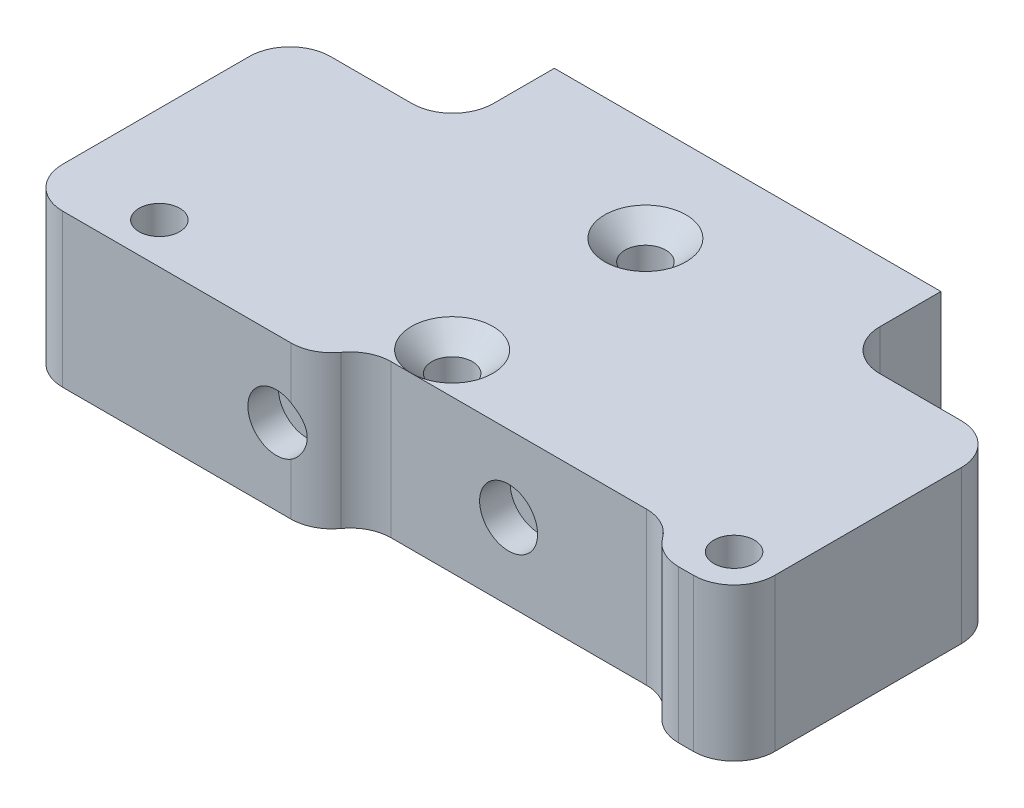
SolidWorks part; units mm, degrees
ref_plane "Front Plane" through (0, 0, 0) normal (0, 0, 1) x (1, 0, 0)
ref_plane "Top Plane" through (0, 0, 0) normal (0, 1, 0) x (1, 0, 0)
ref_plane "Right Plane" through (0, 0, 0) normal (1, 0, 0) x (0, 0, -1)
sketch "Sketch1" plane through (0, 0, 0) normal (0, 1, 0) x (1, 0, 0)
  line L1 (0, 0) -> (-70, 0)
  line L2 (0, 0) -> (0, 34)
  line L3 (0, 34) -> (-70, 34)
  line L4 (-70, 0) -> (-70, 34)
  circle A0 centre (-35.05, 24) radius 2
  circle A1 centre (-35.05, 5) radius 2
  dimension "D5" = 4
  dimension "D6" = 4
  dimension "D7" = 34.95
  dimension "D8" = 34.95
  dimension "D1" = 34
  dimension "D2" = 70
  dimension "D3" = 10
  dimension "D4" = 5
extrude "Boss-Extrude1" add sketch "Sketch1" along normal blind 15
sketch "Sketch4" plane through (0, 0, -34) normal (0, 0, -1) x (-1, 0, 0)
  line L0 (0, 15) -> (70, 15) construction
  line L1 (0, 15) -> (0, 0) construction
  line L2 (70, 15) -> (70, 0) construction
  circle A0 centre (7.5, 10.15) radius 2.5
  circle A1 centre (62.5, 10.15) radius 2.5
  dimension "D3" = 5
  dimension "D5" = 7.5
  dimension "D6" = 5
  dimension "D1" = 4.85
  dimension "D2" = 7.5
  dimension "D4" = 4.85
sketch "Sketch5" plane through (0, 0, 0) normal (0, 0, 1) x (1, 0, 0)
  line L0 (-70, 0) -> (0, 0) construction
  line L1 (-70, 15) -> (-70, 0) construction
  line L2 (0, 15) -> (0, 0) construction
  line L3 (-70, 15) -> (0, 15) construction
  circle A0 centre (-62.5, 10.15) radius 4.3
  circle A1 centre (-7.5, 10.15) radius 4.3
  dimension "D1" = 8.6
  dimension "D3" = 7.5
  dimension "D4" = 7.5
  dimension "D5" = 4.85
  dimension "D6" = 8.6
  dimension "D2" = 10.15
sketch "Sketch6" plane through (0, 0, 0) normal (0, 0, 1) x (1, 0, 0)
  line L4 (-70, 0) -> (0, 0)
  line L5 (0, 0) -> (0, 15)
  line L6 (0, 15) -> (-70, 15)
  line L7 (-70, 15) -> (-70, 0)
  line L8 (-70, 0) -> (0, 0)
  line L9 (0, 0) -> (0, 15)
  line L10 (0, 15) -> (-70, 15)
  line L11 (-70, 15) -> (-70, 0)
  dimension "D1" = 0
extrude "Boss-Extrude2" add sketch "Sketch6" along normal blind 5 contours L8 L9 L10 L11
sketch "Sketch3" plane through (0, 15, 0) normal (0, 1, 0) x (1, 0, 0)
  line L0 (0, -5) -> (0, 34) construction
  line L3 (56.0549, 7.6668) -> (-275.4464, 7.6668) construction
  line L4 (0, -5) -> (-70, -5) construction
  circle A0 centre (-4, 1.67) radius 2
  circle A1 centre (-60.5, 1.67) radius 2
  circle A2 centre (-4, 1.67) radius 6 construction
  dimension "D1" = 4
  dimension "D2" = 4
  dimension "D3" = 6.67
  dimension "D4" = 4
  dimension "D5" = 6.67
  dimension "D6" = 56.5
  dimension "D7" = 4
extrude "Cut-Extrude2" cut sketch "Sketch3" against normal blind 15
sketch "Sketch8" plane through (0, 15, 0) normal (0, 1, 0) x (1, 0, 0)
  line L0 (-19.5, -5) -> (-19.5, 0)
  line L1 (0, -5) -> (-70, -5) construction
  line L2 (-19.5, 0) -> (-13.5, 0)
  line L3 (-13.5, -5) -> (-13.5, 0)
  line L4 (-13.5, -5) -> (-19.5, -5)
  line L5 (0, -5) -> (0, 34) construction
  dimension "D1" = 6
  dimension "D2" = 5
  dimension "D3" = 13.5
extrude "Cut-Extrude3" cut sketch "Sketch8" against normal blind 15
sketch "Sketch9" plane through (0, 15, 0) normal (0, 1, 0) x (1, 0, 0)
  line L0 (-19.5, -5) -> (-70, -5) construction
  line L1 (-29, -5) -> (-41, -5)
  line L2 (-29, -5) -> (-29, 1)
  line L3 (-29, 1) -> (-41, 1)
  line L4 (-41, -5) -> (-41, 1)
  line L5 (-35, 1) -> (-35, 34) construction
  line L6 (0, 34) -> (-70, 34) construction
  dimension "D1" = 12
  dimension "D2" = 6
extrude "Cut-Extrude4" cut sketch "Sketch9" against normal blind 15
sketch "Sketch10" plane through (0, 0, 0) normal (0, -1, 0) x (1, 0, 0)
  line L0 (0, -34) -> (-70, -34) construction
  line L1 (0, -34) -> (-16, -34)
  line L2 (0, -34) -> (0, -24)
  line L3 (0, -24) -> (-16, -24)
  line L4 (-16, -34) -> (-16, -24)
  line L5 (0, 5) -> (0, -34) construction
  line L6 (-35, -34) -> (-35, -1) construction
  line L7 (-29, -1) -> (-41, -1) construction
  line L8 (-70, -34) -> (-54, -34)
  line L9 (-70, -34) -> (-70, -24)
  line L10 (-54, -34) -> (-54, -24)
  line L11 (-70, -24) -> (-54, -24)
  dimension "D1" = 16
  dimension "D2" = 10
extrude "Cut-Extrude5" cut sketch "Sketch10" against normal blind 17
sketch "Sketch12" plane through (0, 0, 5) normal (0, 0, 1) x (1, 0, 0)
  line L0 (-44.5, 0) -> (-44.5, 15) construction
  line L1 (-41, 15) -> (-70, 15) construction
  line L2 (-41, 0) -> (-41, 15) construction
  line L3 (-70, 0) -> (-41, 0) construction
  line L4 (-25, 7.5) -> (-25, 0) construction
  line L7 (-16, 0) -> (-54, 0) construction
  line L8 (0, 15) -> (0, 0) construction
  circle A0 centre (-44.5, 7.5) radius 1.5
  circle A2 centre (-25, 7.5) radius 1.5
  dimension "D2" = 3
  dimension "D3" = 25
  dimension "D1" = 3.5
  dimension "D4" = 7.5
extrude "Cut-Extrude6" cut sketch "Sketch12" against normal blind 41
sketch "Sketch13" plane through (0, 15, 0) normal (0, 1, 0) x (1, 0, 0)
  line L0 (-13.5, -5) -> (-13.5, 0) construction
  line L1 (-13.5, -5) -> (-41, -5)
  line L2 (-13.5, -5) -> (-13.5, 1)
  line L3 (-13.5, 1) -> (-41, 1)
  line L4 (-41, -5) -> (-41, 1)
  line L5 (-41, 1) -> (-41, -5) construction
  line L6 (-16, 34) -> (-54, 34) construction
  dimension "D1" = 6
  dimension "D2" = 33
extrude "Cut-Extrude7" cut sketch "Sketch13" against normal blind 20
sketch "Sketch14" plane through (0, 0, 0) normal (0, -1, 0) x (-1, 0, 0)
  line L0 (0, -5) -> (0, 24) construction
  line L1 (0, -5) -> (13.5, -5)
  line L2 (0, -5) -> (0, -2.33)
  line L3 (0, -2.33) -> (13.5, -2.33)
  line L4 (13.5, -5) -> (13.5, -2.33)
  line L5 (13.5, -5) -> (13.5, 1) construction
  line L6 (0, 24) -> (16, 24) construction
  line L7 (70, -5) -> (41, -5) construction
  line L8 (70, -5) -> (41, -5)
  line L9 (70, -5) -> (70, -2.33)
  line L10 (70, -2.33) -> (41, -2.33)
  line L11 (41, -5) -> (41, -2.33)
  line L12 (70, 24) -> (70, -5) construction
  line L13 (41, 1) -> (41, -5) construction
  circle A0 centre (4.5, 1.67) radius 2 construction
  dimension "D1" = 4
  dimension "D3" = 22.33
  dimension "D4" = 4
  dimension "D2" = 4.5
  dimension "D5" = 2.67
  dimension "D6" = 2.67
extrude "Cut-Extrude8" cut sketch "Sketch14" against normal blind 17
fillet "Fillet2" radius 4 4 edges at (-70, 7.5, -24) (0, 7.5, -24) (0, 7.5, 2.33) (-70, 7.5, 2.33)
sketch "Sketch16" plane through (0, 0, 0) normal (0, -1, 0) x (1, 0, 0)
  line L0 (-13.5, 2.33) -> (-13.5, -1) construction
  line L1 (-13.5, 2.33) -> (-8, 2.33)
  line L2 (-13.5, 2.33) -> (-13.5, -1)
  line L3 (-13.5, -1) -> (-8, -1)
  line L4 (-8, 2.33) -> (-8, -1)
  line L5 (-13.5, 2.33) -> (-4, 2.33) construction
  circle A0 centre (-4, -1.67) radius 2 construction
  dimension "D1" = 4
  dimension "D2" = 3.33
extrude "Cut-Extrude10" cut sketch "Sketch16" against normal blind 18
fillet "Fillet4" radius 4 4 edges at (-16, 7.5, -24) (-54, 7.5, -24) (-41, 7.5, -1) (-8, 7.5, -1)
fillet "Fillet5" radius 4 2 edges at (-41, 7.5, 2.33) (-8, 7.5, 2.33)
sketch "Sketch17" plane through (0, 0, -1) normal (0, 0, 1) x (1, 0, 0)
  line L0 (-11.9435, 0) -> (-37.0565, 0) construction
  line L1 (-11.9435, 0) -> (-11.9435, 15) construction
  circle A0 centre (-25.5, 7.5) radius 2.85
  dimension "D1" = 5.7
  dimension "D2" = 7.5
  dimension "D3" = 13.5565
extrude "Cut-Extrude11" cut sketch "Sketch17" against normal blind 3
sketch "Sketch18" plane through (0, 0, 2.33) normal (0, 0, 1) x (1, 0, 0)
  line L0 (-66, 0) -> (-43.552, 0) construction
  line L1 (-66, 15) -> (-66, 0) construction
  circle A0 centre (-45, 7.5) radius 2.8
  dimension "D1" = 5.6
  dimension "D2" = 7.5
  dimension "D3" = 21
extrude "Cut-Extrude12" cut sketch "Sketch18" against normal blind 3
chamfer "Chamfer1" distance 2 angle 45 3 edges at (-35.05, 0, -22) (-35.05, 15, -22) (-35.05, 15, -3)
